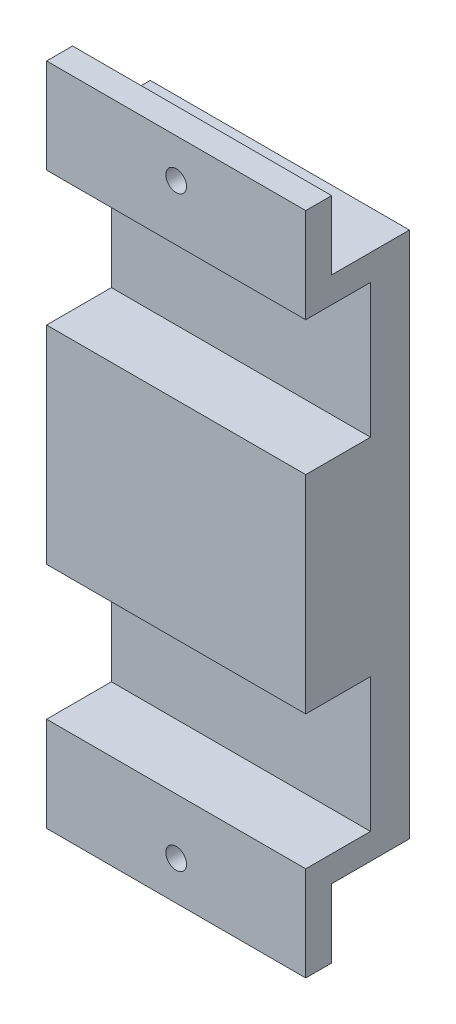
SolidWorks part; units mm, degrees
ref_plane "Front" through (0, 0, 0) normal (0, 0, 1) x (1, 0, 0)
ref_plane "Top" through (0, 0, 0) normal (0, 1, 0) x (1, 0, 0)
ref_plane "Right" through (0, 0, 0) normal (1, 0, 0) x (0, 0, -1)
sketch "Эскиз1" plane through (0, 0, 0) normal (1, 0, 0) x (0, 0, -1)
  line L0 (0, 0) -> (0, 2.5011)
  line L1 (0, 2.5011) -> (1, 2.5011)
  line L2 (1, 2.5011) -> (1, -0.1489)
  line L3 (1, -0.1489) -> (4, -0.1489)
  line L4 (4, -0.1489) -> (4, -10.3239)
  line L5 (4, -10.3239) -> (0, -10.3239)
  line L6 (0, -10.3239) -> (0, -6.3239)
  line L7 (0, -6.3239) -> (2.5, -6.3239)
  line L8 (2.5, -6.3239) -> (2.5, -1.1489)
  line L9 (2.5, -1.1489) -> (0, -1.1489)
  line L10 (0, -1.1489) -> (0, 0)
  dimension "D1" = 1
  dimension "D2" = 3.65
  dimension "D3" = 1.5
  dimension "D4" = 4
  dimension "D5" = 12.825
  dimension "D6" = 1
  dimension "D7" = 4
extrude "Бобышка-Вытянуть1" add sketch "Эскиз1" along normal blind 10
sketch "Эскиз2" plane through (0, 0, -1) normal (0, 0, -1) x (-1, 0, 0)
  line L0 (-10, 2.5011) -> (0, 2.5011) construction
  line L1 (-10, -0.1489) -> (-10, 2.5011) construction
  circle A0 centre (-5, 1.0011) radius 0.4
  dimension "D1" = 0.8
  dimension "D2" = 1.5
  dimension "D3" = 5
extrude "Вырез-Вытянуть1" cut sketch "Эскиз2" against normal through all
mirror "Зеркальное отражение1" about plane through (10, -10.3239, -4) normal (0, 1, 0) of "Вырез-Вытянуть1", "Бобышка-Вытянуть1"
